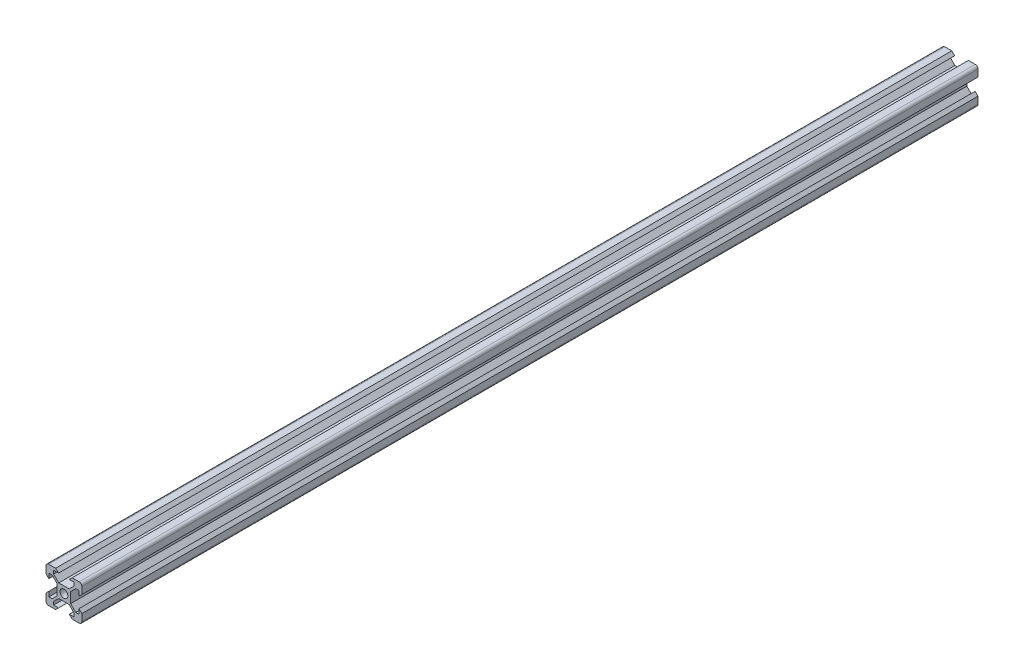
SolidWorks part; units mm, degrees
ref_plane "Front Plane" through (0, 0, 0) normal (0, 0, 1) x (1, 0, 0)
ref_plane "Top Plane" through (0, 0, 0) normal (0, 1, 0) x (1, 0, 0)
ref_plane "Right Plane" through (0, 0, 0) normal (1, 0, 0) x (0, 0, -1)
sketch "Sketch1" plane through (0, 0, 0) normal (0, 0, 1) x (1, 0, 0)
  line L0 (-5.7847, 7.544) -> (-11.512, 13.2713)
  line L1 (-7.544, 7.544) -> (7.544, 7.544)
  line L2 (-7.544, 7.544) -> (-7.544, -7.544)
  line L3 (-7.544, -7.544) -> (7.544, -7.544)
  line L4 (7.544, 7.544) -> (7.544, -7.544)
  line L5 (-7.544, 7.544) -> (7.544, -7.544) construction
  line L6 (-7.544, -7.544) -> (7.544, 7.544) construction
  line L7 (-11.512, 13.2713) -> (-11.512, 16.8)
  line L8 (-11.512, 16.8) -> (-6.052, 16.8)
  line L9 (-6.052, 16.8) -> (-9.252, 20)
  line L10 (-9.252, 20) -> (-17, 20)
  line L11 (-20, 17) -> (-20, 9.252)
  line L12 (-20, 9.252) -> (-16.8, 6.052)
  line L13 (-16.8, 6.052) -> (-16.8, 11.512)
  line L14 (-16.8, 11.512) -> (-13.2713, 11.512)
  line L15 (-13.2713, 11.512) -> (-7.544, 5.7847)
  line L16 (-19.1213, 19.1213) -> (0, 0) construction
  line L17 (13.2713, 11.512) -> (16.8, 11.512)
  line L18 (20, 9.252) -> (20, 17)
  line L19 (17, 20) -> (9.252, 20)
  line L20 (9.252, 20) -> (6.052, 16.8)
  line L21 (6.052, 16.8) -> (11.512, 16.8)
  line L22 (11.512, 16.8) -> (11.512, 13.2713)
  line L23 (11.512, 13.2713) -> (5.7847, 7.544)
  line L24 (7.544, 5.7847) -> (13.2713, 11.512)
  line L25 (16.8, 11.512) -> (16.8, 6.052)
  line L26 (16.8, 6.052) -> (20, 9.252)
  line L27 (19.1213, 19.1213) -> (0, 0) construction
  line L28 (11.512, -13.2713) -> (11.512, -16.8)
  line L29 (9.252, -20) -> (17, -20)
  line L30 (20, -17) -> (20, -9.252)
  line L31 (20, -9.252) -> (16.8, -6.052)
  line L32 (16.8, -6.052) -> (16.8, -11.512)
  line L33 (16.8, -11.512) -> (13.2713, -11.512)
  line L34 (13.2713, -11.512) -> (7.544, -5.7847)
  line L35 (5.7847, -7.544) -> (11.512, -13.2713)
  line L36 (11.512, -16.8) -> (6.052, -16.8)
  line L37 (6.052, -16.8) -> (9.252, -20)
  line L38 (19.1213, -19.1213) -> (0, 0) construction
  line L39 (-13.2713, -11.512) -> (-16.8, -11.512)
  line L40 (-20, -9.252) -> (-20, -17)
  line L41 (-17, -20) -> (-9.252, -20)
  line L42 (-9.252, -20) -> (-6.052, -16.8)
  line L43 (-6.052, -16.8) -> (-11.512, -16.8)
  line L44 (-11.512, -16.8) -> (-11.512, -13.2713)
  line L45 (-11.512, -13.2713) -> (-5.7847, -7.544)
  line L46 (-7.544, -5.7847) -> (-13.2713, -11.512)
  line L47 (-16.8, -11.512) -> (-16.8, -6.052)
  line L48 (-16.8, -6.052) -> (-20, -9.252)
  line L49 (-19.1213, -19.1213) -> (0, 0) construction
  circle A0 centre (0, 0) radius 4.4
  arc A1 (-17, 20) -> (-20, 17) centre (-17, 17) ccw
  arc A2 (20, 17) -> (17, 20) centre (17, 17) ccw
  arc A3 (17, -20) -> (20, -17) centre (17, -17) ccw
  arc A4 (-20, -17) -> (-17, -20) centre (-17, -17) ccw
  point P66 (0, 0)
  dimension "D1" = 8.8
  dimension "D8" = 3
  dimension "D2" = 15.088
  dimension "D3" = 2.488
  dimension "D4" = 8.488
  dimension "D5" = 3.2
  dimension "D6" = 20
  dimension "D7" = 15.2
  dimension "D9" = 4
extrude "Boss-Extrude1" add sketch "Sketch1" along normal mid plane 1000 contours L10 A1 L11 L12 L13 L14 L15 L2 L1 L0 L7 L8 L9 | L18 A2 L19 L20 L21 L22 L23 L1 L4 L24 L17 L25 L26 | L40 A4 L41 L42 L43 L44 L45 L3 L2 L46 L39 L47 L48 | L29 A3 L30 L31 L32 L33 L34 L4 L3 L35 L28 L36 L37 | L4 L1 L2 L3 A0 region at (-14.3184, 14.3184, 0) region at (0, 7.3306, 0) region at (14.3184, 14.3184, 0) region at (-14.3184, -14.3184, 0) region at (14.3184, -14.3184, 0)
equation "\"longitud\"= 800"
